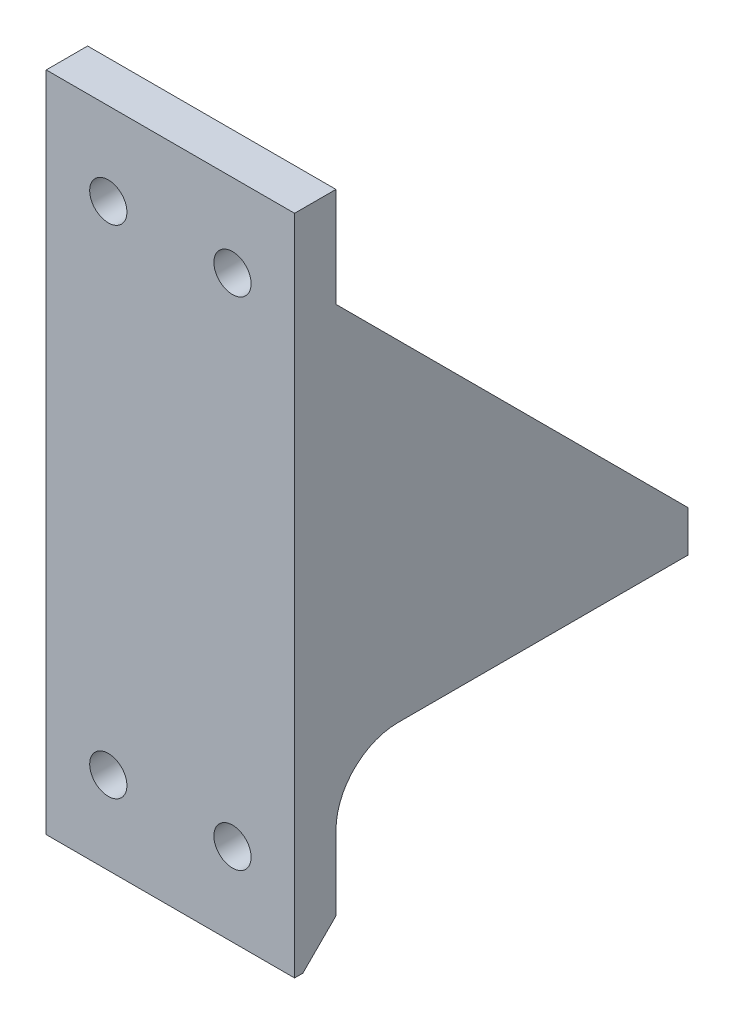
SolidWorks part; units mm, degrees
ref_plane "Front Plane" through (0, 0, 0) normal (0, 0, 1) x (1, 0, 0)
ref_plane "Top Plane" through (0, 0, 0) normal (0, 1, 0) x (1, 0, 0)
ref_plane "Right Plane" through (0, 0, 0) normal (1, 0, 0) x (0, 0, -1)
sketch "Sketch1" plane through (0, 0, 0) normal (0, 0, 1) x (1, 0, 0)
  line L5 (-30, -80) -> (30, -80)
  line L6 (-30, -80) -> (-30, 80)
  line L7 (-30, 80) -> (30, 80)
  line L8 (30, -80) -> (30, 80)
  line L9 (-30, -80) -> (30, 80) construction
  line L10 (-30, 80) -> (30, -80) construction
  point P0 (0, 0)
  dimension "D1" = 160
  dimension "D2" = 60
extrude "Boss-Extrude1" add sketch "Sketch1" along normal blind 10
sketch "Sketch2" plane through (0, 0, 0) normal (1, 0, 0) x (0, 0, -1)
  line L0 (0, -80) -> (0, 80) construction
  line L2 (0, -29.048) -> (0, -39.048)
  line L3 (0, -39.048) -> (85, -39.048)
  line L4 (85, -29.048) -> (85, -39.048)
  line L6 (-5, -80) -> (-5, -60) construction
  line L7 (-10, -80) -> (0, -80) construction
  line L8 (-5, -117.628) -> (-5, -60) construction
  line L9 (-5, -117.628) -> (85, -117.628) construction
  line L10 (85, -29.048) -> (0, 55.952)
  line L11 (0, -29.048) -> (0, 55.952)
  dimension "D1" = 10
  dimension "D2" = 20
  dimension "D4" = 78.58
  dimension "D5" = 85
  dimension "D6" = 45
  dimension "D3" = 57.628
extrude "Boss-Extrude2" add sketch "Sketch2" along normal up to surface and the other way up to surface up to face at (30, 0, 5) other way up to face at (-30, 0, 5)
sketch "Sketch3" plane through (0, -39.048, 0) normal (0, -1, 0) x (1, 0, 0)
  line L1 (-10.3187, -34.7563) -> (10.3188, -34.7563) construction
  line L2 (-10.3187, -34.7563) -> (-10.3187, -74.4438) construction
  line L3 (-10.3187, -74.4438) -> (10.3188, -74.4438) construction
  line L4 (10.3188, -34.7563) -> (10.3188, -74.4438) construction
  line L5 (-10.3187, -34.7563) -> (10.3188, -74.4438) construction
  line L6 (-10.3187, -74.4438) -> (10.3188, -34.7563) construction
  line L7 (-15.0813, -80) -> (15.0812, -80) construction
  line L8 (-15.0813, -80) -> (-15.0813, -29.2) construction
  line L9 (-15.0813, -29.2) -> (15.0812, -29.2) construction
  line L10 (15.0812, -80) -> (15.0812, -29.2) construction
  line L11 (-15.0813, -80) -> (15.0812, -29.2) construction
  line L12 (-15.0813, -29.2) -> (15.0812, -80) construction
  line L13 (30, -85) -> (-30, -85) construction
  circle A0 centre (-10.3187, -34.7563) radius 2.38
  circle A1 centre (10.3188, -34.7563) radius 2.38
  circle A2 centre (10.3188, -74.4438) radius 2.38
  circle A3 centre (-10.3187, -74.4438) radius 2.38
  point P0 (0, -54.6)
  point P10 (0, -54.6)
  dimension "D3" = 4.76
  dimension "D1" = 20.6375
  dimension "D2" = 39.6875
  dimension "D4" = 50.8
  dimension "D5" = 30.1625
  dimension "D6" = 5
extrude "Cut-Extrude1" cut sketch "Sketch3" against normal up to next
chamfer "Chamfer1" distance 8 angle 45 1 edges at (0, -80, 0)
sketch "Sketch4" plane through (0, 0, 0) normal (0, 0, -1) x (-1, 0, 0)
  line L0 (-30, 60) -> (30, 60) construction
  line L1 (-30, 55.952) -> (-30, 80) construction
  line L2 (30, 80) -> (30, 55.952) construction
  line L3 (-30, 80) -> (30, 80) construction
  line L4 (30, -60) -> (-30, -60) construction
  line L5 (30, -39.048) -> (30, -72) construction
  line L6 (-30, -72) -> (-30, -39.048) construction
  line L7 (30, -80) -> (-30, -80) construction
  circle A0 centre (-15, -60) radius 4.5
  circle A1 centre (15, -60) radius 4.5
  circle A2 centre (-15, 60) radius 4.5
  circle A3 centre (15, 60) radius 4.5
  point P24 (0, 0)
  point P26 (0, 0)
  dimension "D2" = 20
  dimension "D3" = 9
  dimension "D1" = 20
  dimension "D4" = 30
  dimension "D5" = 15
extrude "Cut-Extrude2" cut sketch "Sketch4" against normal up to next
sketch "Sketch5" plane through (0, 80, 0) normal (0, 1, 0) x (1, 0, 0)
  circle A0 centre (-10.3187, 74.4438) radius 7.5
  circle A1 centre (10.3188, 74.4438) radius 7.5
  circle A2 centre (-10.3187, 34.7563) radius 7.5
  circle A3 centre (10.3188, 34.7563) radius 7.5
  dimension "D1" = 15
extrude "Cut-Extrude4" cut sketch "Sketch5" against normal offset from surface (114.048 mm away) 5 contours A2 | A0 | A1 | A3 up to face at (-10.3187, -39.048, -37.1363)
sketch "Sketch6" plane through (0, 0, 0) normal (0, 0, -1) x (-1, 0, 0)
  circle A0 centre (-15, 60) radius 7.5
  circle A1 centre (15, 60) radius 7.5
  dimension "D1" = 15
extrude "Cut-Extrude5" cut sketch "Sketch6" along normal blind 5
fillet "Fillet1" radius 15 1 edges at (0, -39.048, 0)
equation "\"Thicknes\"=10"
equation "\"D1@Sketch2\"=\"Thicknes\""
equation "\"D1@Sketch3\"=20.6375"
equation "\"D5@Sketch4\"=\"D4@Sketch4\"/2"
